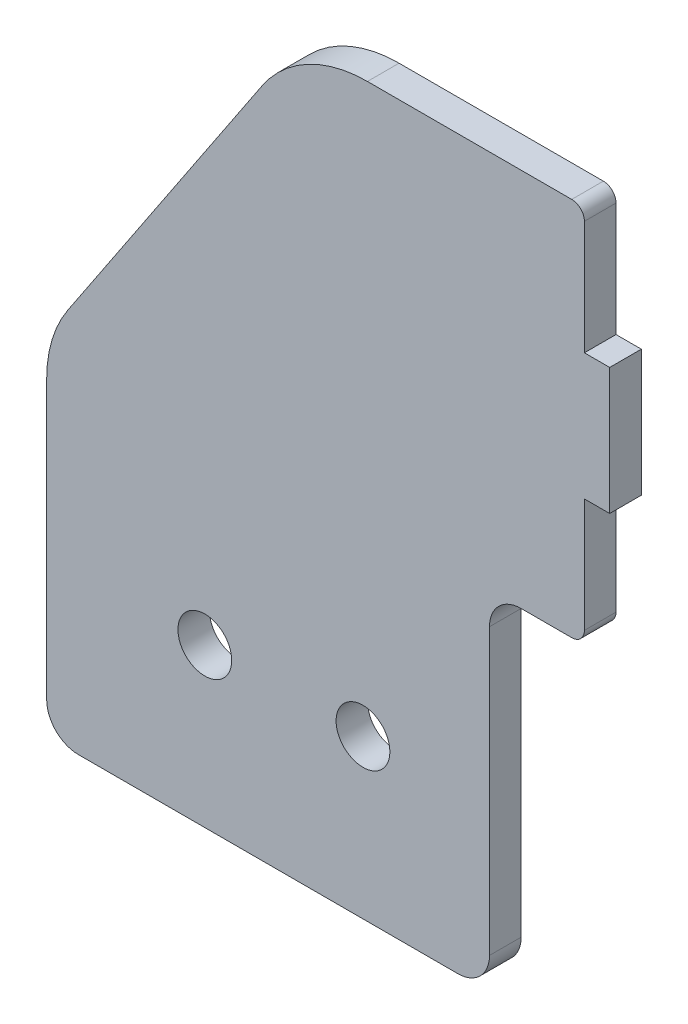
SolidWorks part; units mm, degrees
ref_plane "Ön Düzlem" through (0, 0, 0) normal (0, 0, 1) x (1, 0, 0)
ref_plane "Üst Düzlem" through (0, 0, 0) normal (0, 1, 0) x (1, 0, 0)
ref_plane "Sağ Düzlem" through (0, 0, 0) normal (1, 0, 0) x (0, 0, -1)
sketch "Çizim1" plane through (0, 0, 0) normal (0, 0, 1) x (1, 0, 0)
  line L0 (0, 0) -> (-45, 0)
  line L1 (0, 0) -> (0, -60)
  line L2 (0, -60) -> (-15, -60)
  line L3 (-15, -60) -> (-15, -115)
  line L4 (-15, -115) -> (-85, -115)
  line L6 (-85, -115) -> (-85, -60)
  line L7 (-85, -60) -> (-45, 0)
  dimension "D1" = 70
  dimension "D2" = 45
  dimension "D3" = 60
  dimension "D4" = 55
  dimension "D5" = 55
  dimension "D6" = 40
base flange "Taban-Flanş1" sketch "Çizim1" thickness 5 reverse thickness direction no parameters "D1"=2
sketch "Çizim8" plane through (0, 0, 0) normal (0, 0, 1) x (1, 0, 0)
  line L0 (-85, -115) -> (-15, -115) construction
  line L1 (-85, -60) -> (-85, -115) construction
  circle A0 centre (-35, -90) radius 4.25
  circle A1 centre (-60, -90) radius 4.25
  dimension "D1" = 8.5
  dimension "D2" = 25
  dimension "D3" = 25
  dimension "D4" = 25
extrude "Kes-Ekstrüzyon1" cut sketch "Çizim8" against normal blind 10
fillet "Radyus1" radius 20 2 edges at (-85, -60, -2.5) (-45, 0, -2.5)
fillet "Radyus2" radius 5 3 edges at (-85, -115, -2.5) (-15, -115, -2.5) (-15, -60, -2.5)
fillet "Radyus3" radius 2 2 edges at (0, -60, -2.5) (0, 0, -2.5)
sketch "Çizim10" plane through (0, 0, 0) normal (1, 0, 0) x (0, 0, -1)
  line L0 (0, -58) -> (0, -2) construction
  line L1 (0, -20) -> (5, -20)
  line L2 (0, -20) -> (0, -40)
  line L3 (0, -40) -> (5, -40)
  line L4 (5, -20) -> (5, -40)
  line L5 (5, -58) -> (5, -2) construction
  line L6 (0, 0) -> (5, 0) construction
  dimension "D1" = 20
  dimension "D2" = 20
extrude "Yükseklik-Ekstrüzyon1" add sketch "Çizim10" along normal blind 4
sketch "Büküm-Çizgileri1" [suppressed] plane through (0, 0, 0) normal (0, 1, 0) x (1, 0, 0)
sketch "Sınırlandırma-Kutusu1" [suppressed] plane through (0, 0, 0) normal (0, 1, 0) x (1, 0, 0)
sheet metal parameters "Sac-Levha1" thickness 5 parameters "D1"=2
flat pattern "Düz-Çoğaltma1" [suppressed]
sketch "Büküm-Çizgileri2" plane through (0, 0, 0) normal (0, 0, 1) x (1, 0, 0)
  line L0 (-30, -60) -> (-30, 0) construction
  line L1 (-30, -60) -> (-30, 0) construction
sketch3d "Sınırlandırma-Kutusu2" [suppressed]
  line L0 (-120, -115, 0) -> (0, -115, 0) construction
  line L1 (-120, 0, 0) -> (0, 0, 0) construction
  line L2 (-120, -115, 0) -> (-120, 0, 0) construction
  line L3 (0, -115, 0) -> (0, 0, 0) construction
sheet metal parameters "Sac-Levha2" thickness 5 parameters "D1"=2
flat pattern "Düz-Çoğaltma1"
sketch "Büküm-Çizgileri2" plane through (-35.1051, 0, 0) normal (1, 0, 0) x (0, 0, -1)
sketch3d "Sınırlandırma-Kutusu2" [suppressed]
  line L0 (0, -115, 0) -> (0, 0, 0) construction
  line L1 (-85, -115, 0) -> (-85, 0, 0) construction
  line L2 (0, -115, 0) -> (-85, -115, 0) construction
  line L3 (0, 0, 0) -> (-85, 0, 0) construction
sheet metal parameters "Sac-Levha4" thickness 5 parameters "D1"=2
flat pattern "Düz-Çoğaltma1"
sketch "Büküm-Çizgileri2" plane through (-35.1051, 0, 0) normal (1, 0, 0) x (0, 0, -1)
sketch3d "Sınırlandırma-Kutusu2" [suppressed]
  line L0 (4, -115, 0) -> (4, 0, 0) construction
  line L1 (-85, -115, 0) -> (-85, 0, 0) construction
  line L2 (4, -115, 0) -> (-85, -115, 0) construction
  line L3 (4, 0, 0) -> (-85, 0, 0) construction
